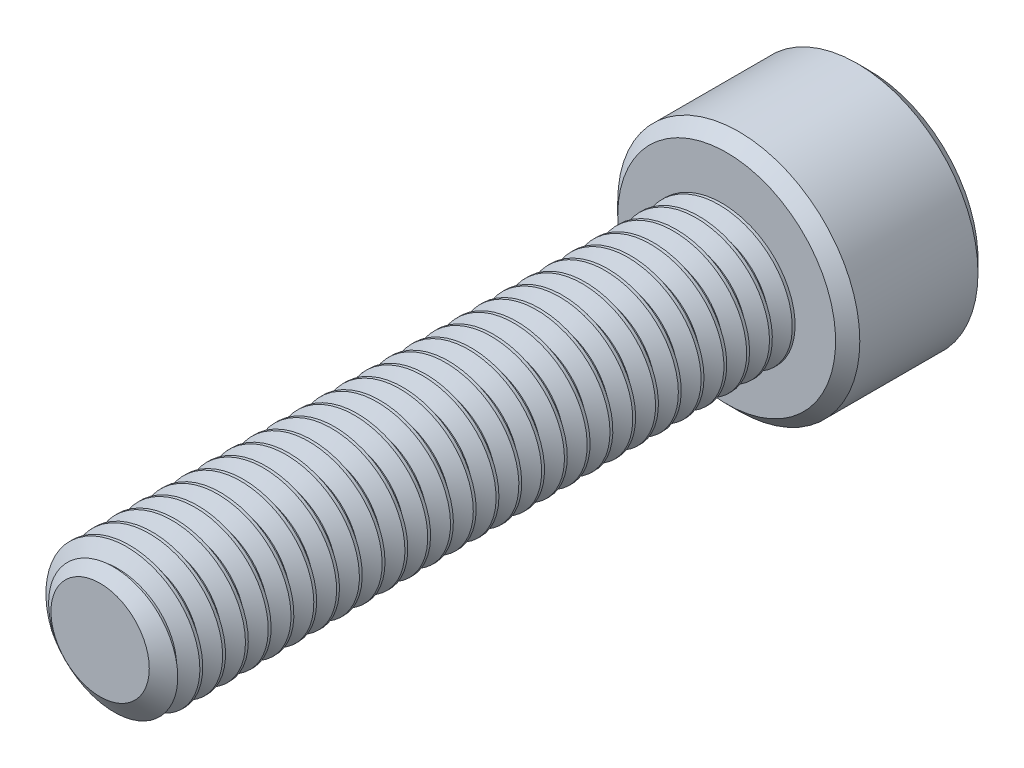
SolidWorks part; units mm, degrees
note: '?' marks a value the reader was unsure of.
other "DetailItem1"
ref_plane "Front Plane" through (0, 0, 0) normal (0, 0, 1) x (1, 0, 0)
ref_plane "Top Plane" through (0, 0, 0) normal (0, 1, 0) x (1, 0, 0)
ref_plane "Right Plane" through (0, 0, 0) normal (1, 0, 0) x (0, 0, -1)
sketch "Sketch1" plane through (0, 0, 0) normal (0, 0, 1) x (1, 0, 0)
  circle A0 centre (0, 0) radius 2.5
  dimension "OD" = 5
extrude "Extrude1" add sketch "Sketch1" against normal blind 22
sketch "Sketch2" plane through (0, 0, 0) normal (0, 0, 1) x (1, 0, 0)
  circle A0 centre (0, 0) radius 2.5 construction
  circle A1 centre (0, 0) radius 2.5
curve "Helix/Spiral1" pitch 0.8 height 22.8 turns 28.5 parameters "pitch"=0.8
sketch "Sketch3" plane through (0, 0, 0) normal (1, 0, 0) x (0, 0, -1)
  line L0 (-0.7, 2.5) -> (-0.4, 1.9804)
  line L1 (-0.4, 1.9804) -> (-0.3, 1.9804)
  line L2 (-0.3, 1.9804) -> (0, 2.5)
  line L3 (-0.7, 2.5) -> (0, 2.5)
  line L4 (-0.35, 2.5) -> (-0.35, 1.9804) construction
  line L5 (-0.55, 2.2402) -> (-0.15, 2.2402) construction
  line L6 (0, 2.5) -> (0, -2.5) construction
  dimension "D1" = 0.1
  dimension "D2" = 0.4
  dimension "D3" = 60
sweep "Cut-Sweep1" cut profiles "Sketch3" path "Helix/Spiral1"
sketch "Sketch4" plane through (0, 0, 0) normal (1, 0, 0) x (0, 0, -1)
  line L0 (0.5417, 2.5) -> (0, 1.7264)
  line L1 (0, 1.7264) -> (0, 2.5)
  line L2 (0.5417, 2.5) -> (0, 2.5)
  line L3 (-0.7, 2.5) -> (0, 2.5) construction
  line L4 (0, 0) -> (7.0209, 0) construction
  dimension "D1" = 55
  dimension "D2" = 0.254
revolve "Cut-Revolve1" cut sketch "Sketch4" angle 360 about L4
sketch "Sketch6" plane through (0, 0, -22) normal (0, 0, -1) x (-1, 0, 0)
  circle A0 centre (0, 0) radius 4.25
  dimension "head dia" = 8.5
extrude "Extrude2" add sketch "Sketch6" along normal blind 5
sketch "Sketch7" plane through (0, 0, -27) normal (0, 0, -1) x (-1, 0, 0)
  line L1 (0, 2.3094) -> (-2, 1.1547)
  line L2 (-2, 1.1547) -> (-2, -1.1547)
  line L3 (-2, -1.1547) -> (0, -2.3094)
  line L4 (0, -2.3094) -> (2, -1.1547)
  line L5 (2, -1.1547) -> (2, 1.1547)
  line L6 (2, 1.1547) -> (0, 2.3094)
  circle A0 centre (0, 0) radius 2 construction
  dimension "hex dia" = 4
extrude "Cut-Extrude1" cut sketch "Sketch7" against normal blind 3
sketch "Sketch8" plane through (0, 0, -27) normal (0, 0, -1) x (-1, 0, 0)
  circle A0 centre (0, 0) radius 2.3094
extrude "Cut-Extrude2" cut sketch "Sketch8" against normal through all draft 45
chamfer "Chamfer1" distance 0.425 angle 45 2 edges at (-4.25, 0, -27) (-4.25, 0, -22)
sketch "Sketch10" plane through (0, 0, -22) normal (0, 0, 1) x (1, 0, 0)
  circle A1 centre (0, 0) radius 2.5
  circle A2 centre (0, 0) radius 2.5
  dimension "D1" = 0
ref_plane "Plane1" through (0, 0, 0) normal (0, 0, 1) x (1, 0, 0)
extrude "partial thread" [suppressed] add sketch "Sketch10" along normal up to surface (13 mm away) separate body
chamfer "Chamfer2" [suppressed] distance 0.1 angle 45
combine bodies "Combine1" [suppressed] operation type? add bodies to combine 107 108
sketch "Sketch9" plane through (0, 0, 0) normal (1, 0, 0) x (0, 0, -1)
  line L0 (0, 2.5) -> (0, -2.5) construction
  line L1 (2, 2.5) -> (2, -2.5) construction
  dimension "D1" = 2
equation "\"D3@Helix/Spiral1\" = \"screw length@Extrude1\"+\"pitch@Helix/Spiral1\""
equation "\"D1@Sketch3\" = \"pitch@Helix/Spiral1\"*.125"
equation "\"D2@Sketch3\" = \"pitch@Helix/Spiral1\"*.5"
equation "\"D1@Cut-Extrude1\" = \"hex dia@Sketch7\"*.75"
equation "\"D1@Chamfer1\" = \"head dia@Sketch6\"*.05"
equation "\"D1@Sketch9\" = \"pitch@Helix/Spiral1\"*2.5"
equation "\"D1@Chamfer2\"=\"OD@Sketch1\"*.02"
